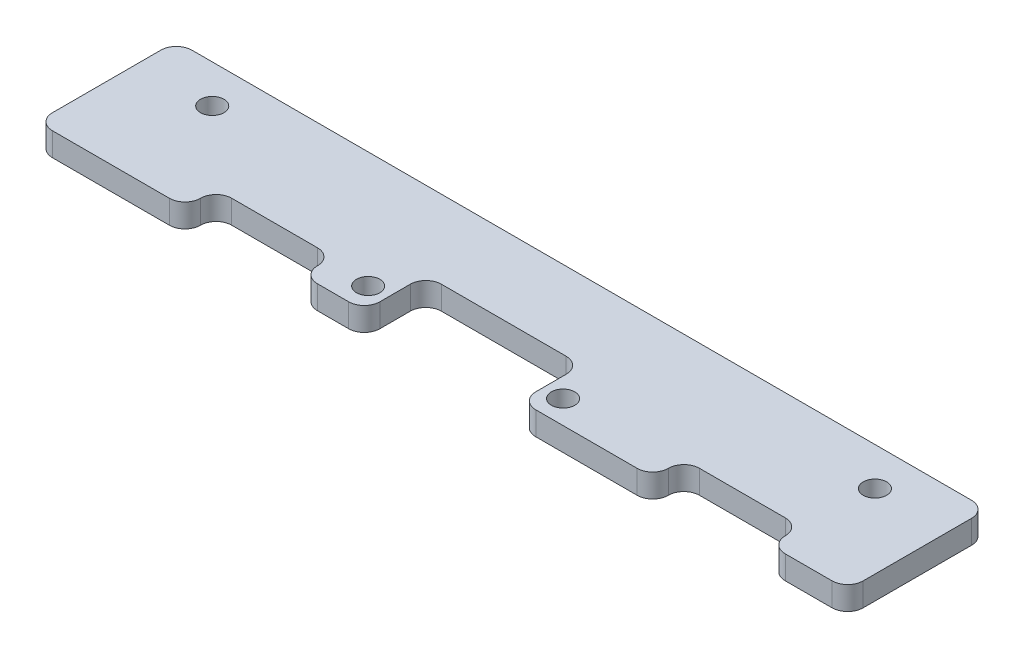
SolidWorks part; units mm, degrees
material "Thornel Mat VMA"
ref_plane "前视基准面" through (0, 0, 0) normal (0, 0, 1) x (1, 0, 0)
ref_plane "上视基准面" through (0, 0, 0) normal (0, 1, 0) x (1, 0, 0)
ref_plane "右视基准面" through (0, 0, 0) normal (1, 0, 0) x (0, 0, -1)
other "Configuration Table"
sketch "草图1" plane through (0, 0, 0) normal (0, 1, 0) x (1, 0, 0)
  line L0 (0, 0) -> (0, 21.9469) construction
  line L1 (-52, 0) -> (52, 0)
  line L2 (52, 0) -> (52, -17.9)
  line L3 (52, -17.9) -> (10, -17.9)
  line L4 (10, -17.9) -> (10, -10)
  line L5 (10, -10) -> (-10, -10)
  line L6 (-10, -17.9) -> (-10, -10)
  line L7 (-52, -17.9) -> (-10, -17.9)
  line L8 (-52, 0) -> (-52, -17.9)
  circle A0 centre (-12.5, -14.9) radius 1.5
  circle A1 centre (12.5, -14.9) radius 1.5
  circle A2 centre (-42.5, -4.9) radius 1.5
  circle A3 centre (42.5, -4.9) radius 1.5
  point P9 (0, -10)
  dimension "D4" = 3
  dimension "D5" = 25
  dimension "D7" = 3
  dimension "D8" = 85
  dimension "D1" = 10
  dimension "D2" = 17.9
  dimension "D3" = 20
  dimension "D6" = 104
  dimension "D9" = 4.9
  dimension "D10" = 3
extrude "凸台-拉伸1" add sketch "草图1" along normal blind 3
sketch "草图2" plane through (0, 3, 0) normal (0, 1, 0) x (1, 0, 0)
  line L0 (0, 0) -> (0, 19.3534) construction
  line L1 (-33, -17.9) -> (-33, -13.9)
  line L2 (-52, -17.9) -> (-10, -17.9) construction
  line L3 (-33, -13.9) -> (-18, -13.9)
  line L4 (-18, -13.9) -> (-18, -17.9)
  line L5 (-52, 0) -> (-52, -17.9) construction
  line L6 (42, -17.9) -> (42, -13.9)
  line L7 (10, -17.9) -> (52, -17.9) construction
  line L8 (42, -13.9) -> (27, -13.9)
  line L9 (27, -13.9) -> (27, -17.9)
  line L10 (52, -17.9) -> (52, 0) construction
  line L11 (27, -17.9) -> (42, -17.9)
  line L12 (-18, -17.9) -> (-33, -17.9)
  dimension "D1" = 19
  dimension "D2" = 15
  dimension "D3" = 4
  dimension "D4" = 10
  dimension "D5" = 15
extrude "切除-拉伸1" cut sketch "草图2" against normal blind 3
fillet "圆角1" radius 2 16 edges at (52, 1.5, 17.9) (10, 1.5, 17.9) (10, 1.5, 10) (-10, 1.5, 10) (-10, 1.5, 17.9) (-52, 1.5, 17.9) (52, 1.5, 0) (-52, 1.5, 0) (-33, 1.5, 13.9) (-18, 1.5, 13.9) (-18, 1.5, 17.9) (27, 1.5, 17.9) (27, 1.5, 13.9) (42, 1.5, 13.9) (42, 1.5, 17.9) (-33, 1.5, 17.9)
